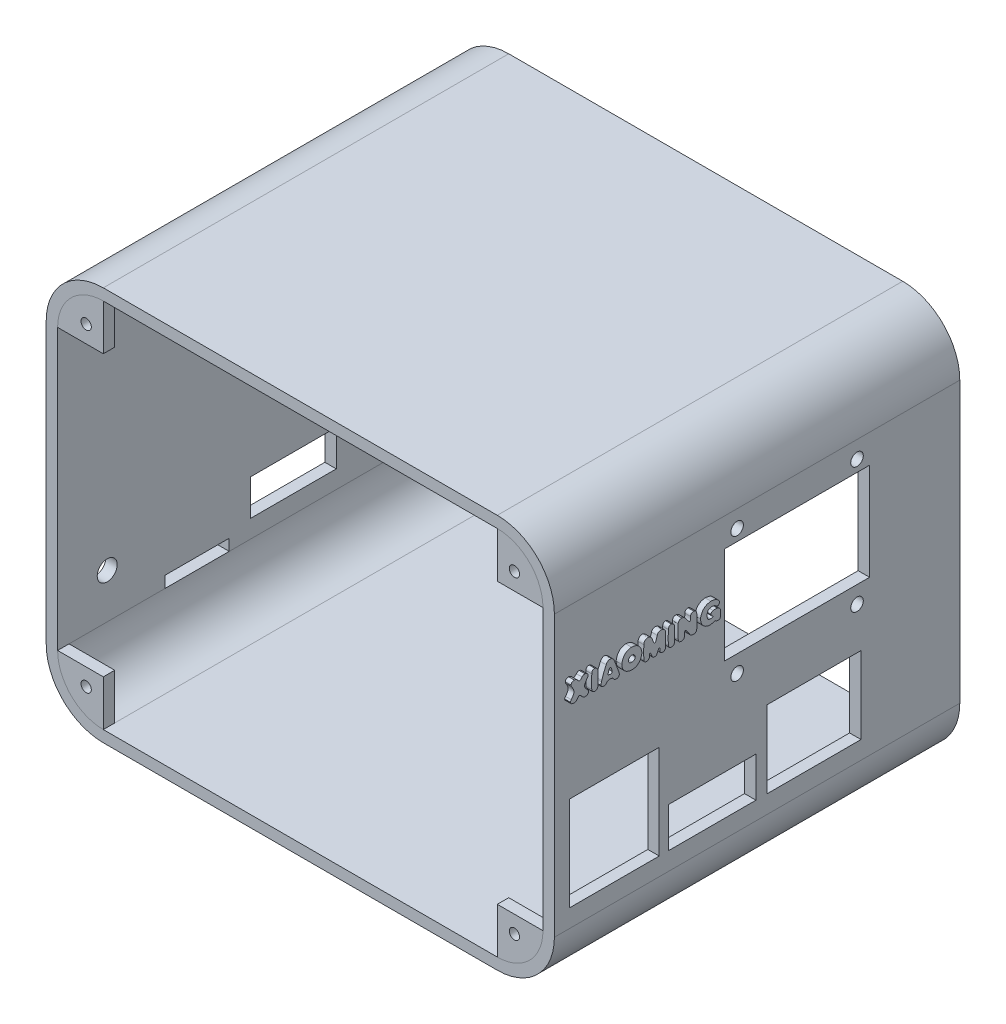
SolidWorks part; units mm, degrees
ref_plane "前视基准面" through (0, 0, 0) normal (0, 0, 1) x (1, 0, 0)
ref_plane "上视基准面" through (0, 0, 0) normal (0, 1, 0) x (1, 0, 0)
ref_plane "右视基准面" through (0, 0, 0) normal (1, 0, 0) x (0, 0, -1)
sketch "草图1" plane through (0, 0, 0) normal (0, 0, 1) x (1, 0, 0)
  line L0 (8, 67) -> (77, 67)
  line L1 (8, 0) -> (77, 0)
  line L2 (0, 8) -> (0, 57)
  line L3 (8, 65) -> (77, 65)
  line L4 (85, 8) -> (85, 57)
  line L5 (87, 8) -> (87, 57)
  line L6 (8, -2) -> (77, -2)
  line L7 (-2, 8) -> (-2, 57)
  arc A0 (77, 0) -> (85, 8) centre (77, 8) ccw
  arc A1 (0, 57) -> (8, 65) centre (8, 57) cw
  arc A2 (77, 65) -> (85, 57) centre (77, 57) cw
  arc A3 (8, 0) -> (0, 8) centre (8, 8) cw
  arc A4 (77, 67) -> (87, 57) centre (77, 57) cw
  arc A5 (77, -2) -> (87, 8) centre (77, 8) ccw
  arc A6 (8, -2) -> (-2, 8) centre (8, 8) cw
  arc A7 (-2, 57) -> (8, 67) centre (8, 57) cw
  point P7 (85, 0)
  point P12 (85, 65)
  point P15 (0, 0)
  dimension "D3" = 8
  dimension "D1" = 85
  dimension "D2" = 65
  dimension "D4" = 2
extrude "凸台-拉伸1" add sketch "草图1" against normal blind 71
sketch "草图2" plane through (0, 0, 0) normal (0, 0, 1) x (1, 0, 0)
  line L0 (8, 65) -> (8, 57)
  line L1 (8, 57) -> (0, 57)
  line L2 (42.5, 65) -> (42.5, 0) construction
  line L3 (77, 65) -> (8, 65) construction
  line L4 (8, 0) -> (77, 0) construction
  line L5 (0, 32.5) -> (85, 32.5)
  line L6 (0, 57) -> (0, 8) construction
  line L7 (85, 8) -> (85, 57) construction
  line L8 (77, 57) -> (85, 57)
  line L9 (77, 65) -> (77, 57)
  line L10 (77, 0) -> (77, 8)
  line L11 (77, 8) -> (85, 8)
  line L12 (8, 8) -> (0, 8)
  line L13 (8, 0) -> (8, 8)
  circle A0 centre (5, 60) radius 0.9
  circle A1 centre (80, 60) radius 0.9
  circle A2 centre (80, 5) radius 0.9
  circle A3 centre (5, 5) radius 0.9
  arc M6 (85, 8) -> (77, 0) centre (77, 8) cw
  arc M8 (8, 0) -> (0, 8) centre (8, 8) cw
  arc M10 (0, 57) -> (8, 65) centre (8, 57) cw
  arc M12 (77, 65) -> (85, 57) centre (77, 57) cw
  dimension "D1" = 1.8
  dimension "D2" = 3
  dimension "D3" = 3
extrude "凸台-拉伸2" add sketch "草图2" against normal blind 2 separate body contours L1 L0 A0 M10 | L9 L8 A1 M12 | L13 L12 A3 M8 | L11 L10 A2 M6 region at (7.8869, 61, 0) region at (77.1131, 61, 0) region at (77.1131, 4, 0) region at (7.8869, 4, 0)
sketch "草图3" plane through (0, 0, -71) normal (0, 0, -1) x (-1, 0, 0)
  line L0 (-77, 65) -> (-77, 57)
  line L1 (-77, 57) -> (-85, 57)
  line L2 (-42.5, 65) -> (-42.5, 0) construction
  line L5 (-85, 32.5) -> (0, 32.5) construction
  line L6 (-85, 8) -> (-85, 57) construction
  line L7 (0, 57) -> (0, 8) construction
  line L8 (-77, 65) -> (-8, 65) construction
  line L9 (-8, 0) -> (-77, 0) construction
  line L10 (-8, 57) -> (0, 57)
  line L11 (-8, 65) -> (-8, 57)
  line L12 (-8, 8) -> (0, 8)
  line L13 (-8, 0) -> (-8, 8)
  line L14 (-77, 8) -> (-85, 8)
  line L15 (-77, 0) -> (-77, 8)
  circle A0 centre (-80, 60) radius 0.9
  circle A2 centre (-5, 60) radius 0.9
  circle A3 centre (-5, 5) radius 0.9
  circle A4 centre (-80, 5) radius 0.9
  arc M7 (-77, 0) -> (-85, 8) centre (-77, 8) cw
  arc M9 (-85, 57) -> (-77, 65) centre (-77, 57) cw
  arc M11 (-8, 65) -> (0, 57) centre (-8, 57) cw
  arc M13 (0, 8) -> (-8, 0) centre (-8, 8) cw
extrude "凸台-拉伸3" add sketch "草图3" against normal blind 2 contours L1 L0 A0 M9 | L11 L10 A2 M11 | L13 L12 A3 M13 | L15 L14 A4 M7 region at (77.1131, 61, -71) region at (7.8869, 61, -71) region at (4, 7.8869, -71) region at (77.1131, 4, -71)
sketch "草图5" plane through (87, 0, 0) normal (1, 0, 0) x (0, 0, -1)
  line L4 (2.66, 27.14) -> (17.86, 27.14)
  line L5 (2.66, 27.14) -> (2.66, 11.14)
  line L6 (2.66, 11.14) -> (17.86, 11.14)
  line L7 (17.86, 27.14) -> (17.86, 11.14)
  line L8 (20.5, 17.64) -> (35.3, 17.64)
  line L9 (20.5, 17.64) -> (20.5, 11.14)
  line L10 (20.5, 11.14) -> (35.3, 11.14)
  line L11 (35.3, 17.64) -> (35.3, 11.14)
  line L12 (37.2, 24.14) -> (53.2, 24.14)
  line L13 (37.2, 24.14) -> (37.2, 11.14)
  line L14 (37.2, 11.14) -> (53.2, 11.14)
  line L15 (53.2, 24.14) -> (53.2, 11.14)
extrude "切除-拉伸1" cut sketch "草图5" against normal up to next (2 mm away)
sketch "草图6" plane through (-2, 0, 0) normal (-1, 0, 0) x (0, 0, 1)
  line L4 (-48.8, 17.44) -> (-33.8, 17.44)
  line L5 (-48.8, 17.44) -> (-48.8, 11.14)
  line L6 (-48.8, 11.14) -> (-33.8, 11.14)
  line L7 (-33.8, 17.44) -> (-33.8, 11.14)
  line L8 (-30.0532, 10) -> (-18.8, 10)
  line L9 (-30.0532, 10) -> (-30.0532, 8)
  line L10 (-30.0532, 8) -> (-18.8, 8)
  line L11 (-18.8, 10) -> (-18.8, 8)
extrude "切除-拉伸2" cut sketch "草图6" against normal up to next (2 mm away)
sketch "草图7" plane through (87, 0, 0) normal (1, 0, 0) x (0, 0, -1)
  line L0 (2.66, 27.14) -> (2.66, 11.14) construction
  line L1 (2.66, 27.64) -> (18.36, 27.64)
  line L2 (2.66, 27.64) -> (2.66, 11.14)
  line L3 (2.66, 11.14) -> (18.36, 11.14)
  line L4 (18.36, 27.64) -> (18.36, 11.14)
  line L5 (17.86, 27.14) -> (2.66, 27.14) construction
  line L6 (17.86, 11.14) -> (17.86, 27.14) construction
  line L7 (35.3, 17.64) -> (20.5, 17.64) construction
  line L8 (35.3, 11.14) -> (20, 11.14)
  line L9 (35.3, 11.14) -> (35.3, 18.14)
  line L10 (35.3, 18.14) -> (20, 18.14)
  line L11 (20, 11.14) -> (20, 18.14)
  line L12 (37.2, 11.14) -> (53.7, 11.14)
  line L13 (37.2, 11.14) -> (37.2, 24.64)
  line L14 (37.2, 24.64) -> (53.7, 24.64)
  line L15 (53.7, 11.14) -> (53.7, 24.64)
  line L16 (20.5, 17.64) -> (20.5, 11.14) construction
  line L17 (53.2, 24.14) -> (37.2, 24.14) construction
  line L18 (53.2, 11.14) -> (53.2, 24.14) construction
  point P28 (53.2, 17.64)
  dimension "D1" = 0.5
  dimension "D2" = 0.5
  dimension "D3" = 0.5
  dimension "D4" = 0.5
  dimension "D5" = 0.5
  dimension "D6" = 0.5
extrude "切除-拉伸3" cut sketch "草图7" against normal up to next (87 mm away)
sketch "草图9" plane through (87, 0, 0) normal (1, 0, 0) x (0, 0, -1)
  line L0 (0, 8) -> (0, 57) construction
  line L1 (71, 57) -> (0, 57) construction
  line L3 (29.8, 52) -> (55.2, 52)
  line L4 (29.8, 52) -> (29.8, 35)
  line L5 (29.8, 35) -> (55.2, 35)
  line L6 (55.2, 52) -> (55.2, 35)
  circle A0 centre (32, 54) radius 1.1
  circle A1 centre (53, 54) radius 1.1
  circle A2 centre (32, 32) radius 1.1
  circle A3 centre (53, 32) radius 1.1
  dimension "D1" = 2.2
  dimension "D2" = 2.2
  dimension "D3" = 2.2
  dimension "D4" = 21
  dimension "D5" = 22
  dimension "D6" = 32
  dimension "D7" = 3
  dimension "D10" = 2.2
  dimension "D11" = 2
  dimension "D12" = 2.2
  dimension "D8" = 25.4
  dimension "D9" = 17
extrude "切除-拉伸4" cut sketch "草图9" against normal up to next (2 mm away)
sketch "草图10" plane through (87, 0, 0) normal (1, 0, 0) x (0, 0, -1)
  text T0 "XIAOMING" font "华光胖头鱼_CNKI" height 3.5
extrude "凸台-拉伸4" add sketch "草图10" along normal blind 1
sketch "草图11" plane through (-2, 0, 0) normal (-1, 0, 0) x (0, 0, 1)
  circle A0 centre (-8.6848, 15.8133) radius 1.75
  dimension "D1" = 3.5
extrude "切除-拉伸5" cut sketch "草图11" against normal up to next (2 mm away)
